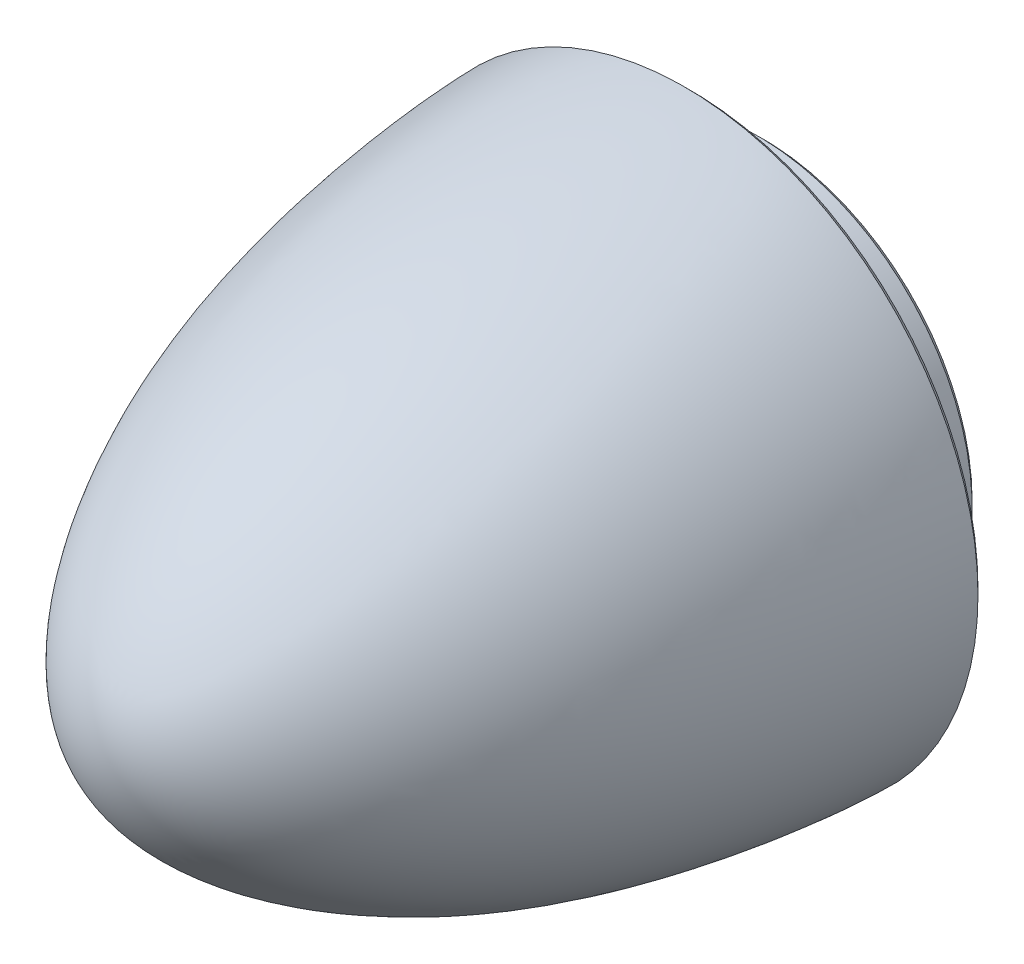
SolidWorks part; units mm, degrees
ref_plane "Front Plane" through (0, 0, 0) normal (0, 0, 1) x (1, 0, 0)
ref_plane "Top Plane" through (0, 0, 0) normal (0, 1, 0) x (1, 0, 0)
ref_plane "Right Plane" through (0, 0, 0) normal (1, 0, 0) x (0, 0, -1)
sketch "Sketch2" plane through (0, 0, 0.1005) normal (0, 1, 0) x (1, 0, 0)
  line L0 (0, 0) -> (0, 25.4)
  line L1 (0, 12.7) -> (10.6627, 12.7) construction
  line L3 (0, 0) -> (0, 25.4) construction
  line L7 (0, 25.4) -> (12.7, 25.4)
  spline S1 degree 3 poles (0, 0) (4.2518, -0.0002) (11.6078, 10.0817) (12.7, 23.2927) (12.7, 25.4) knots 0.5 0.5 0.5 0.5 0.789003 1 1 1 1
revolve "Revolve5" add sketch "Sketch2" angle 360 about L3
sketch "Sketch3" plane through (0, 0, -25.2995) normal (0, 0, -1) x (-1, 0, 0)
  circle A0 centre (0, 0) radius 9.271
  dimension "D1" = 18.542
extrude "Boss-Extrude1" add sketch "Sketch3" along normal blind 3.175
fillet "Fillet1" radius 0.254 1 edges at (-9.271, 0, -25.2995)
chamfer "Chamfer1" distance 0.254 angle 45 2 edges at (-9.271, 0, -28.4745) (12.7, 0, -25.2995)
